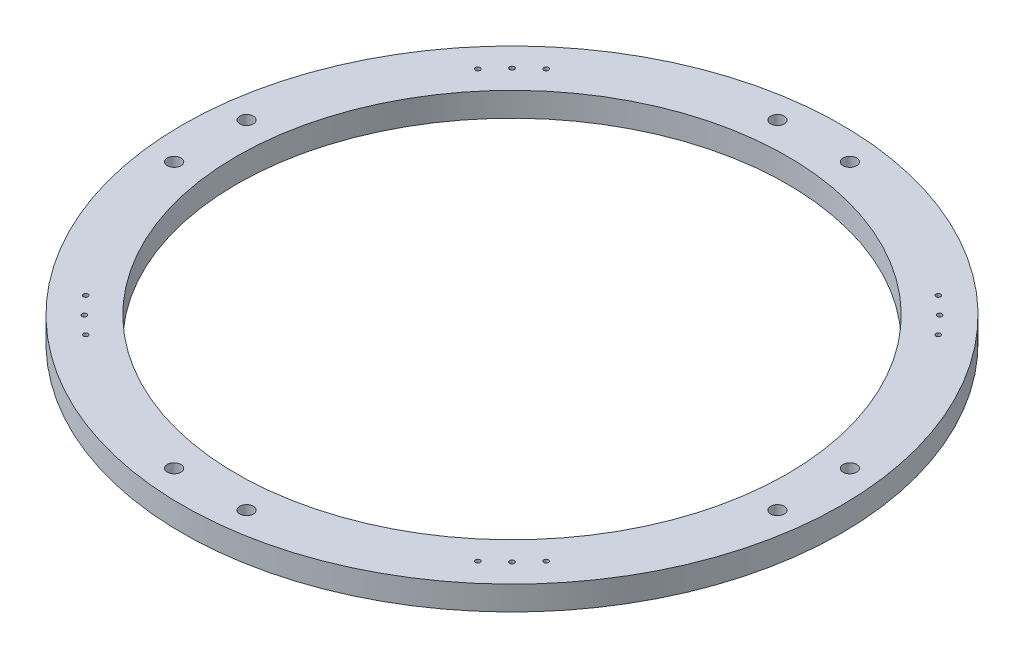
SolidWorks part; units mm, degrees
material "Oak"
ref_plane "Front Plane" through (0, 0, 0) normal (0, 0, 1) x (1, 0, 0)
ref_plane "Top Plane" through (0, 0, 0) normal (0, 1, 0) x (1, 0, 0)
ref_plane "Right Plane" through (0, 0, 0) normal (1, 0, 0) x (0, 0, -1)
sketch "Sketch1" plane through (0, 0, 0) normal (0, 0, 1) x (1, 0, 0)
  line L0 (0, -200000) -> (0, 218797.9879) construction
  line L5 (0, -200000) -> (0, 218797.9879) construction
  line L6 (173.3622, 178.8688) -> (173.3622, 166.1688)
  line L7 (144.7872, 178.8688) -> (173.3622, 178.8688)
  line L8 (173.3622, 166.1688) -> (144.7872, 166.1688)
  line L9 (144.7872, 166.1688) -> (144.7872, 178.8688)
revolve "Revolve1" add sketch "Sketch1" angle 360 about L5
hole_wizard "Tap Drill for M3x0.5 Tap1" positions "Sketch5" profile "Sketch6" hole size "M3x0.5" standard "ANSI Metric" end condition through all
sketch "Sketch5" plane through (0, 178.8688, 0) normal (0, 1, 0) x (1, 0, 0)
  line L0 (0, 0) -> (-112.4828, 112.4828) construction
  point P0 (-112.4828, 112.4828)
  point P3 (-103.1435, 121.104)
  point P6 (-121.104, 103.1435)
  dimension "D1" = 159.0747
sketch "Sketch6" plane through (-112.4828, 178.8688, -112.4828) normal (1, 0, 0) x (0, 0, 1)
  line L0 (0, 0) -> (0, 12.7)
  line L1 (0, 12.7) -> (1.25, 12.7)
  line L2 (1.25, 12.7) -> (1.25, 0)
  line L5 (1.25, 0) -> (0, 0)
  line L11 (0, -6.35) -> (0, 107.95) construction
  dimension "Thru Hole Dia." = 2.5
  dimension "Thru Hole Depth" = 12.7
sketch "Sketch7" plane through (0, 178.8688, 0) normal (0, 1, 0) x (1, 0, 0)
  line L0 (0, 0) -> (158.6742, 0) construction
  line L1 (158.6742, 19.05) -> (158.6742, -19.05) construction
  line L2 (158.6742, -19.05) -> (0, 0) construction
  line L3 (0, 0) -> (158.6742, 19.05) construction
  circle A0 centre (158.6742, -19.05) radius 3.5719
  circle A1 centre (158.6742, 19.05) radius 3.5719
  point P6 (158.6742, 0)
  dimension "D3" = 7.1437
  dimension "D1" = 38.1
  dimension "D2" = 159.8137
extrude "Cut-Extrude1" cut sketch "Sketch7" against normal through all
pattern_circular "CirPattern1" count 4 over 360 about axis through (0, -200000, 0) along (0, -1, 0) of "Tap Drill for M3x0.5 Tap1", "Cut-Extrude1"
